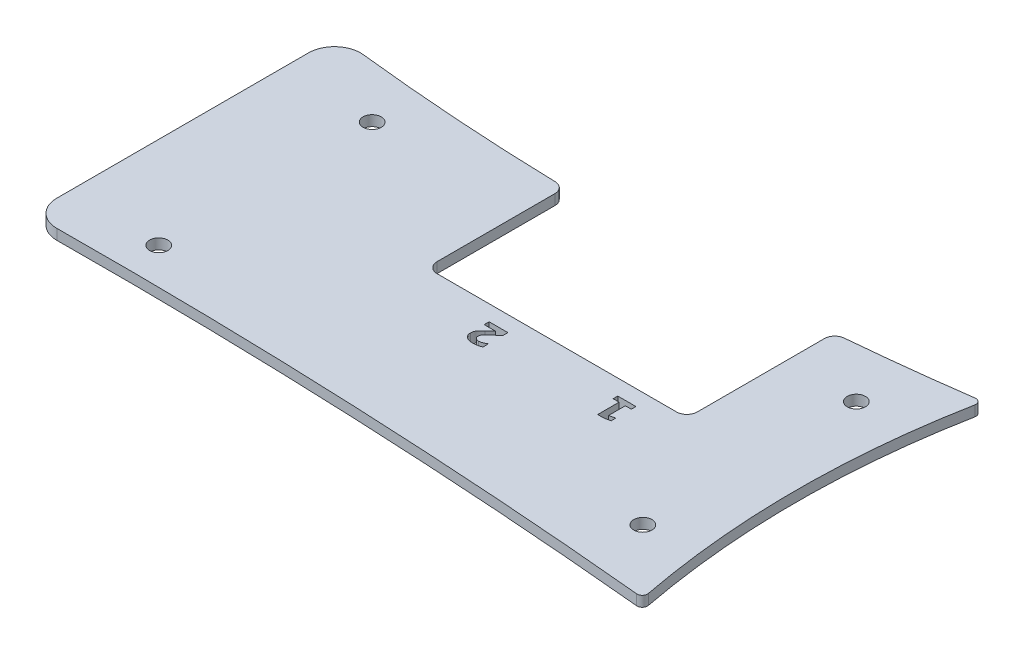
SolidWorks part; units mm, degrees
ref_plane "Alzado" through (0, 0, 0) normal (0, 0, 1) x (1, 0, 0)
ref_plane "Planta" through (0, 0, 0) normal (0, 1, 0) x (1, 0, 0)
ref_plane "Vista lateral" through (0, 0, 0) normal (1, 0, 0) x (0, 0, -1)
sketch "Croquis1" plane through (0, 0, 0) normal (0, 1, 0) x (1, 0, 0)
  line L1 (-5.038, 53.3629) -> (-5.038, 4.9999)
  circle A12 centre (105.5937, 6.9652) radius 2.175
  circle A13 centre (105.5937, 47.9652) radius 2.175
  circle A14 centre (12.5937, 47.9652) radius 2.175
  arc A15 (117.5244, 58.7899) -> (117.5365, -3.9226) centre (281.1497, 27.4652) ccw
  arc A16 (117.5244, 58.7899) -> (116.4035, 59.9683) centre (116.5423, 58.978) ccw
  arc A17 (0.5157, 58.3321) -> (116.4035, 59.9683) centre (51.9534, 519.9785) ccw
  arc A18 (0.5157, 58.3321) -> (-5.038, 53.3629) centre (-0.038, 53.3629) ccw
  arc A19 (-5.038, 4.9999) -> (0, 0) centre (-0.038, 4.9999) ccw
  arc A20 (116.4593, -5.1065) -> (0, 0) centre (8.6221, -1133.9022) ccw
  arc A21 (116.4593, -5.1065) -> (117.5365, -3.9226) centre (116.5544, -4.1111) ccw
  circle A22 centre (12.5937, 6.9652) radius 2.175
extrude "Saliente-Extruir1" add sketch "Croquis1" along normal blind 2
sketch "Croquis2" plane through (0, 2, 0) normal (0, 1, 0) x (1, 0, 0)
  circle A0 centre (12.5937, 6.9652) radius 2.175 construction
  circle A1 centre (105.5937, 6.9652) radius 2.175 construction
  circle A2 centre (105.5937, 47.9652) radius 2.175 construction
  circle A3 centre (12.5937, 47.9652) radius 2.175 construction
  circle A4 centre (12.5937, 6.9652) radius 2.175
  circle A5 centre (105.5937, 6.9652) radius 2.175
  circle A6 centre (105.5937, 47.9652) radius 2.175
  circle A7 centre (12.5937, 47.9652) radius 2.175
  circle A8 centre (12.5937, 47.9652) radius 1.75
  circle A9 centre (105.5937, 47.9652) radius 1.75
  circle A10 centre (105.5937, 6.9652) radius 1.75
  circle A11 centre (12.5937, 6.9652) radius 1.75
  dimension "D1" = 3.5
extrude "Saliente-Extruir2" add sketch "Croquis2" against normal up to surface (2 mm away) up to face at (56.7437, 0, -28.0629)
sketch "Croquis3" plane through (0, 0, 0) normal (0, -1, 0) x (1, 0, 0)
  line L1 (116.5423, -58.978) -> (8.2155, -58.978) construction
  line L7 (92.0423, -58.978) -> (42.0423, -58.978)
  line L8 (92.0423, -58.978) -> (92.0423, -28.978)
  line L9 (92.0423, -28.978) -> (42.0423, -28.978)
  line L10 (42.0423, -58.978) -> (42.0423, -28.978)
  dimension "D4" = 50
  dimension "D5" = 30
  dimension "D6" = 24.5
extrude "Cortar-Extruir1" cut sketch "Croquis3" against normal up to surface (2 mm away) up to face at (56.7437, 2, -28.0629)
fillet "Redondeo1" radius 2 4 edges at (42.0423, 1, -55.5811) (42.0423, 1, -28.978) (92.0423, 1, -57.2085) (92.0423, 1, -28.978)
sketch "Croquis5" plane through (0, 0, 0) normal (0, -1, 0) x (1, 0, 0)
  line L0 (90.0423, -28.978) -> (44.0423, -28.978) construction
  text T0 "1" font "DejaVu Sans" height 5
  text T1 "2" font "DejaVu Sans" height 5
  point P2 (40.7618, -11.5293)
  point P3 (53.1685, -20.362)
  point P4 (84.9442, -25.3337)
  point P5 (54.484, -26.5349)
  point P8 (84.6425, -26.7775)
  point P9 (84.4456, -24.71)
  point P10 (82.2313, -25.978)
  point P11 (56.4726, -25.978)
  point P12 (0, 0)
  point P13 (86.068, -25.978)
  point P14 (61.221, -25.978)
  dimension "D1" = 3
  dimension "D2" = 3
extrude "Cortar-Extruir2" cut sketch "Croquis5" against normal up to surface (2 mm away) up to face at (61.8822, 2, -35.5879)
